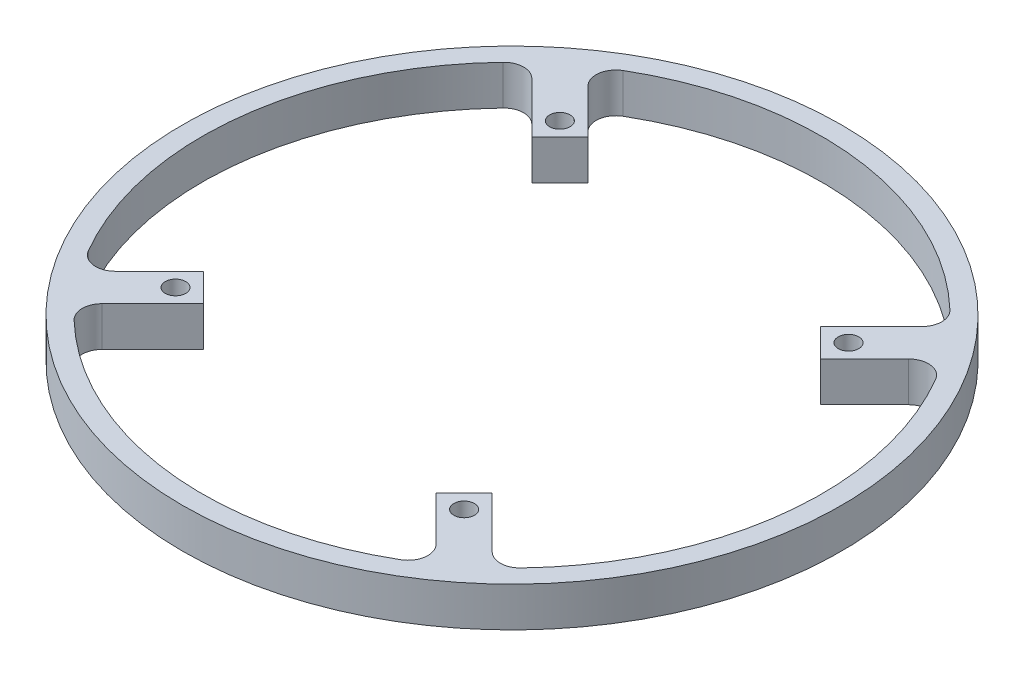
SolidWorks part; units mm, degrees
material "6061-T6 (SS)"
ref_plane "Front Plane" through (0, 0, 0) normal (0, 0, 1) x (1, 0, 0)
ref_plane "Top Plane" through (0, 0, 0) normal (0, 1, 0) x (1, 0, 0)
ref_plane "Right Plane" through (0, 0, 0) normal (1, 0, 0) x (0, 0, -1)
sketch "Sketch2" plane through (0, 0, 0) normal (1, 0, 0) x (0, 0, -1)
  line L0 (-55, 0) -> (-83.0999, 0)
  line L1 (-83.0999, 0) -> (-83.0999, 10)
  line L2 (-83.0999, 10) -> (-55, 10)
  line L5 (-55, 10) -> (-55, 0)
  dimension "D1" = 83.0999
  dimension "D2" = 10
  dimension "D3" = 55
ref_axis "Axis1" through (0, 3.6789, 0) along (0, 1, 0)
revolve "Revolve1" add sketch "Sketch2" angle 360 about axis through (0, 3.6789, 0) along (0, 1, 0)
sketch "Sketch9" plane through (0, 0, 0) normal (0, 1, 0) x (1, 0, 0)
  line L1 (42.4264, -42.4264) -> (-42.4264, -42.4264) construction
  line L2 (42.4264, -42.4264) -> (42.4264, 42.4264) construction
  line L3 (42.4264, 42.4264) -> (-42.4264, 42.4264) construction
  line L4 (-42.4264, -42.4264) -> (-42.4264, 42.4264) construction
  line L5 (0, 0) -> (0, 27.9091) construction
  line L7 (0, 0) -> (26.5726, 0) construction
  line L11 (-43.4619, 48.4619) -> (-36.3909, 55.533) construction
  line L12 (-43.4619, 48.4619) -> (-36.3909, 41.3909) construction
  line L13 (-36.3909, 55.533) -> (-29.3198, 48.4619) construction
  line L16 (-36.3909, 41.3909) -> (-36.3909, 55.533) construction
  line L18 (-43.4619, 48.4619) -> (-29.3198, 48.4619) construction
  line L20 (-29.3198, 48.4619) -> (-36.3909, 41.3909) construction
  point P3 (-42.4264, 42.4264)
  point P355 (-36.3909, 48.4619)
  dimension "D1" = 1.0355
  dimension "D2" = 60
  dimension "D3" = 6.0355
  dimension "D4" = 6.1237
hole_wizard "#6 (0.204) Diameter Hole1" positions "Sketch12" profile "Sketch13" hole size "#6" standard "ANSI Inch" end condition through all
sketch "Sketch12" plane through (0, 0, 0) normal (0, -1, 0) x (-1, 0, 0)
  point P0 (36.3909, 48.4619)
sketch "Sketch13" plane through (-36.3909, 0, -48.4619) normal (1, 0, 0) x (0, 0, -1)
  line L0 (0, 0) -> (0, 10)
  line L1 (0, 10) -> (2.5908, 10)
  line L2 (2.5908, 10) -> (2.5908, 0)
  line L5 (2.5908, 0) -> (0, 0)
  line L11 (0, -6.35) -> (0, 107.95) construction
  dimension "Thru Hole Dia." = 5.1816
  dimension "Thru Hole Depth" = 10
sketch "Sketch14" plane through (0, 0, 0) normal (0, -1, 0) x (1, 0, 0)
  line L0 (0, 0) -> (-36.3909, -48.4619) construction
  line L1 (-33.0708, -38.0708) -> (-52.6684, -57.6684)
  line L2 (-63.9603, 44.8182) -> (-55.533, 36.3909)
  line L3 (0, 0) -> (-48.4619, 36.3909) construction
  line L4 (-43.4619, -48.4619) -> (-36.3909, -41.3909) construction
  line L5 (-55.533, 36.3909) -> (-48.4619, 29.3198)
  line L6 (-41.3909, 36.3909) -> (-48.4619, 29.3198) construction
  line L7 (-41.3909, 36.3909) -> (-48.4619, 43.4619) construction
  line L8 (-48.4619, 43.4619) -> (-55.533, 36.3909) construction
  line L9 (-48.4619, 29.3198) -> (-55.533, 36.3909) construction
  line L10 (-41.3909, 36.3909) -> (-55.533, 36.3909) construction
  line L11 (-48.4619, 43.4619) -> (-48.4619, 29.3198) construction
  line L12 (-48.4619, 29.3198) -> (-41.3909, 36.3909)
  line L13 (-43.4619, -48.4619) -> (-36.3909, -55.533) construction
  line L14 (0, 0) -> (26.5726, 0) construction
  line L15 (-41.3909, 36.3909) -> (-38.0708, 33.0708)
  arc A0 (-33.0708, -38.0708) -> (-38.0708, 33.0708) centre (0, 0) cw
  arc A1 (-63.9603, 44.8182) -> (-52.6684, -57.6684) centre (0, 0) ccw
  circle A2 centre (0, 0) radius 83.0999 construction
  point P14 (-48.4619, 36.3909)
  dimension "D2" = 5
  dimension "D3" = 50.4288
extrude "Cut-Extrude1" cut sketch "Sketch14" against normal through all
pattern_circular "CirPattern1" count 4 over 360 about axis through (0, 3.6789, 0) along (0, 1, 0) of "Cut-Extrude1", "#6 (0.204) Diameter Hole1"
fillet "Fillet1" radius 5 8 edges at (52.6684, 5, 57.6684) (-52.6684, 5, -57.6684) (57.6684, 5, -52.6684) (-57.6684, 5, 52.6684) (44.8182, 5, 63.9603) (63.9603, 5, -44.8182) (-44.8182, 5, -63.9603) (-63.9603, 5, 44.8182)
equation "\"TubeDiameter\" = 6.5433in"
equation "\"D1@Sketch2\"=\"TubeDiameter\"/2"
